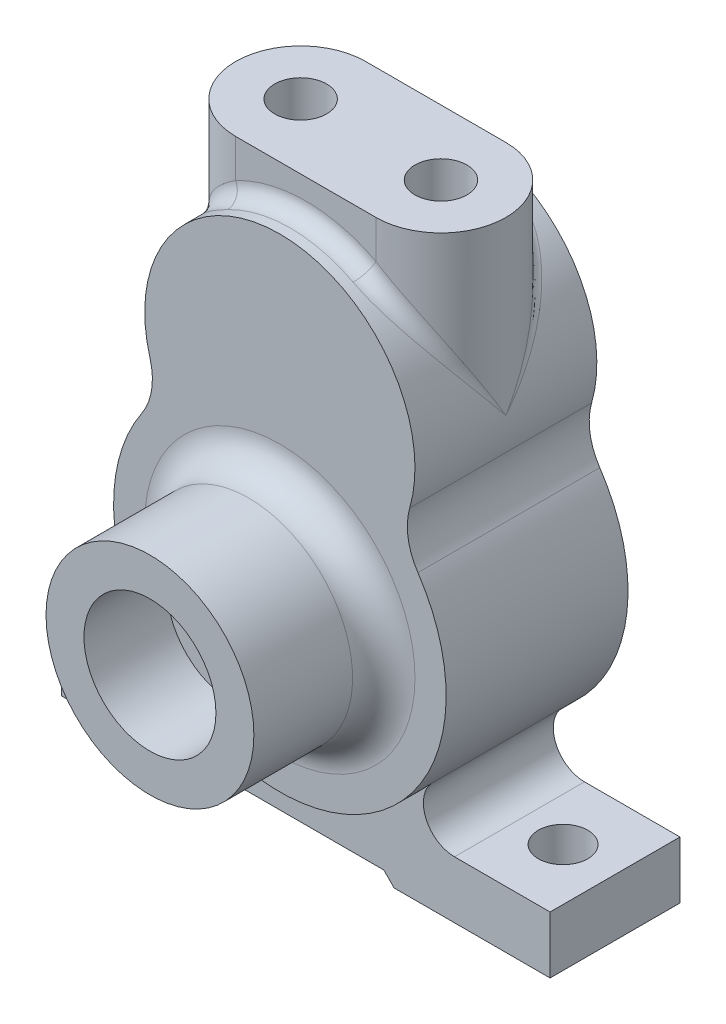
SolidWorks part; units mm, degrees
material "AISI 1020"
ref_plane "Plano frontal" through (0, 0, 0) normal (0, 0, 1) x (1, 0, 0)
ref_plane "Plano superior" through (0, 0, 0) normal (0, 1, 0) x (1, 0, 0)
ref_plane "Plano direito" through (0, 0, 0) normal (1, 0, 0) x (0, 0, -1)
sketch "Esboço1" plane through (0, 0, 0) normal (0, 0, 1) x (1, 0, 0)
  arc A0 (-26.5664, 17.839) -> (26.5664, 17.839) centre (0, 0) ccw
  arc A1 (24.9934, 27.8353) -> (-24.9934, 27.8353) centre (0, 35) ccw
  arc A2 (-24.9934, 27.8353) -> (-26.5664, 17.839) centre (-36.5287, 24.5286) cw
  arc A3 (24.9934, 27.8353) -> (26.5664, 17.839) centre (36.5287, 24.5286) ccw
  dimension "D1" = 64
  dimension "D4" = 52
  dimension "D5" = 12
  dimension "D2" = 0
  dimension "D3" = 35
extrude "Ressalto-extrusão1" add sketch "Esboço1" along normal blind 35
ref_plane "Plano1" through (0, -42, 0) normal (0, 1, 0) x (1, 0, 0)
sketch "Esboço2" plane through (0, -42, 0) normal (0, 1, 0) x (1, 0, 0)
  line L0 (26, 0) -> (-26, 0) construction
  line L1 (-47, -5) -> (47, -5)
  line L2 (-47, -5) -> (-47, -30)
  line L3 (-47, -30) -> (47, -30)
  line L4 (47, -5) -> (47, -30)
  dimension "D1" = 25
  dimension "D2" = 94
  dimension "D3" = 47
  dimension "D4" = 5
extrude "Ressalto-extrusão2" add sketch "Esboço2" along normal blind 11
fillet "Filete1" radius 6 2 edges at (7.9373, -31, 17.5) (-7.9373, -31, 17.5)
ref_plane "Plano2" through (0, 68, 0) normal (0, 1, 0) x (1, 0, 0)
sketch "Esboço3" plane through (0, 68, 0) normal (0, 1, 0) x (1, 0, 0)
  line L0 (-13.5, -17.5) -> (13.5, -17.5) construction
  line L1 (-13.5, -5) -> (13.5, -5)
  line L2 (-13.5, -30) -> (13.5, -30)
  line L3 (26, 0) -> (-26, 0) construction
  arc A0 (-13.5, -5) -> (-13.5, -30) centre (-13.5, -17.5) ccw
  arc A1 (13.5, -30) -> (13.5, -5) centre (13.5, -17.5) ccw
  point P2 (0, -17.5)
  point P7 (-26, -17.5)
  point P8 (26, -17.5)
  dimension "D2" = 52
  dimension "D3" = 12.5
  dimension "D1" = 26
  dimension "D4" = 5
extrude "Ressalto-extrusão3" add sketch "Esboço3" against normal up to surface (10.7795 mm away)
sketch "Esboço4" plane through (0, 68, 0) normal (0, 1, 0) x (1, 0, 0)
  circle A0 centre (-13.5, -17.5) radius 5
  circle A1 centre (13.5, -17.5) radius 5
  dimension "D1" = 10
  dimension "D2" = 10
extrude "Corte-extrusão1" cut sketch "Esboço4" against normal blind 30
sketch "Esboço5" plane through (0, 0, 0) normal (0, 0, -1) x (-1, 0, 0)
  arc A0 (-13.1845, 17.6116) -> (13.1845, 17.6116) centre (0, 0) ccw
  arc A1 (12.3283, 24.8014) -> (-12.3283, 24.8014) centre (0, 35) ccw
  arc A2 (12.3283, 24.8014) -> (13.1845, 17.6116) centre (16.1809, 21.6143) ccw
  arc A3 (-12.3283, 24.8014) -> (-13.1845, 17.6116) centre (-16.1809, 21.6143) cw
  dimension "D1" = 44
  dimension "D2" = 32
  dimension "D3" = 5
extrude "Corte-extrusão2" cut sketch "Esboço5" against normal blind 25
sketch "Esboço6" plane through (0, 0, 35) normal (0, 0, 1) x (1, 0, 0)
  circle A0 centre (0, 0) radius 20
  dimension "D1" = 40
extrude "Ressalto-extrusão4" add sketch "Esboço6" along normal blind 25
sketch "Esboço7" plane through (0, 0, 60) normal (0, 0, 1) x (1, 0, 0)
  circle A0 centre (0, 0) radius 8
  dimension "D1" = 16
extrude "Corte-extrusão3" cut sketch "Esboço7" against normal through all
sketch "Esboço8" plane through (0, 0, 60) normal (0, 0, 1) x (1, 0, 0)
  circle A0 centre (0, 0) radius 12.7
  dimension "D1" = 25.4
extrude "Corte-extrusão4" cut sketch "Esboço8" against normal blind 16
sketch "Esboço9" plane through (0, 0, 30) normal (0, 0, 1) x (1, 0, 0)
  line L0 (-17, -42) -> (-15, -40)
  line L1 (-47, -42) -> (47, -42) construction
  line L2 (-15, -40) -> (15, -40)
  line L3 (15, -40) -> (17, -42)
  line L4 (17, -42) -> (-17, -42)
  dimension "D1" = 2
  dimension "D2" = 17
  dimension "D3" = 34
  dimension "D4" = 45
extrude "Corte-extrusão5" cut sketch "Esboço9" against normal through all
sketch "Esboço10" plane through (0, -42, 0) normal (0, -1, 0) x (1, 0, 0)
  line L0 (-17, 5) -> (-47, 5) construction
  line L1 (47, 5) -> (17, 5) construction
  circle A0 centre (-37, 17.5) radius 4.7625
  circle A1 centre (37, 17.5) radius 4.7625
  dimension "D1" = 37
  dimension "D5" = 9.525
  dimension "D2" = 74
  dimension "D3" = 12.5
  dimension "D4" = 12.5
extrude "Corte-extrusão6" cut sketch "Esboço10" against normal blind 16
sketch "Esboço11" plane through (0, 0, 0) normal (0, 0, -1) x (-1, 0, 0)
  line L0 (0, 0) -> (-39.4712, 0) construction
  line L1 (0, 0) -> (40.0285, 0) construction
  line L2 (0, 0) -> (26.08, -6.9881) construction
  line L3 (0, 0) -> (-26.08, -6.9881) construction
  line L4 (0, 0) -> (0, 35) construction
  line L5 (-11.7949, 35) -> (10.2049, 35) construction
  line L6 (0, 35) -> (14.8492, 49.8492) construction
  line L7 (0, 35) -> (-14.8492, 49.8492) construction
  line L8 (-36.5287, 24.5286) -> (-19.5287, 24.5286) construction
  line L9 (19.5287, 24.5286) -> (36.5287, 24.5286) construction
  circle A0 centre (0, -27) radius 1.5875
  circle A1 centre (-26.08, -6.9881) radius 1.5875
  circle A2 centre (26.08, -6.9881) radius 1.5875
  circle A3 centre (19.5287, 24.5286) radius 1.5875
  circle A4 centre (-19.5287, 24.5286) radius 1.5875
  circle A5 centre (-14.8492, 49.8492) radius 1.5875
  circle A6 centre (14.8492, 49.8492) radius 1.5875
  dimension "D1" = 3.175
  dimension "D2" = 0
  dimension "D3" = 27
  dimension "D4" = 15
  dimension "D5" = 27
  dimension "D6" = 27
  dimension "D7" = 15
  dimension "D8" = 35
  dimension "D9" = 17
  dimension "D10" = 17
  dimension "D13" = 21
  dimension "D14" = 45
  dimension "D15" = 45
  dimension "D16" = 21
extrude "Corte-extrusão7" cut sketch "Esboço11" against normal blind 7
fillet "Filete2" radius 3 6 edges at (22.7562, 47.576, 25.9008) (0, 61, 30) (22.7562, 47.576, 9.0992) (0, 61, 5) (-22.7562, 47.576, 25.9008) (-22.7562, 47.576, 9.0992)
sketch "Esboço12" plane through (0, 0, 25) normal (0, 0, -1) x (-1, 0, 0)
  circle A0 centre (0, 0) radius 18
  dimension "D1" = 36
extrude "Corte-extrusão8" cut sketch "Esboço12" against normal blind 10
sketch3d "3DSketch1"
  point P0 (0, 13, 0)
sketch3d "3DSketch2"
  point P0 (0, 13, 0)
fillet "Filete3" radius 6 1 edges at (20, 0, 35)
sketch "Esboço13" plane through (0, 0, 0) normal (0, 0, -1) x (-1, 0, 0)
  line L1 (-12.8285, 46.3492) -> (-10.8078, 49.8492)
  line L2 (-10.8078, 49.8492) -> (-12.8285, 53.3492)
  line L3 (-12.8285, 53.3492) -> (-16.87, 53.3492)
  line L4 (-16.87, 53.3492) -> (-18.8907, 49.8492)
  line L5 (-18.8907, 49.8492) -> (-16.87, 46.3492)
  line L6 (-16.87, 46.3492) -> (-12.8285, 46.3492)
  line L7 (16.87, 46.3492) -> (18.8907, 49.8492)
  line L8 (18.8907, 49.8492) -> (16.87, 53.3492)
  line L9 (16.87, 53.3492) -> (12.8285, 53.3492)
  line L10 (12.8285, 53.3492) -> (10.8078, 49.8492)
  line L11 (10.8078, 49.8492) -> (12.8285, 46.3492)
  line L12 (12.8285, 46.3492) -> (16.87, 46.3492)
  line L13 (-17.508, 21.0286) -> (-15.4873, 24.5286)
  line L14 (-15.4873, 24.5286) -> (-17.508, 28.0286)
  line L15 (-17.508, 28.0286) -> (-21.5495, 28.0286)
  line L16 (-21.5495, 28.0286) -> (-23.5702, 24.5286)
  line L17 (-23.5702, 24.5286) -> (-21.5495, 21.0286)
  line L18 (-21.5495, 21.0286) -> (-17.508, 21.0286)
  line L19 (-24.0593, -10.4881) -> (-22.0385, -6.9881)
  line L20 (-22.0385, -6.9881) -> (-24.0593, -3.4881)
  line L21 (-24.0593, -3.4881) -> (-28.1007, -3.4881)
  line L22 (-28.1007, -3.4881) -> (-30.1214, -6.9881)
  line L23 (-30.1214, -6.9881) -> (-28.1007, -10.4881)
  line L24 (-28.1007, -10.4881) -> (-24.0593, -10.4881)
  line L25 (2.0207, -30.5) -> (4.0415, -27)
  line L26 (4.0415, -27) -> (2.0207, -23.5)
  line L27 (2.0207, -23.5) -> (-2.0207, -23.5)
  line L28 (-2.0207, -23.5) -> (-4.0415, -27)
  line L29 (-4.0415, -27) -> (-2.0207, -30.5)
  line L30 (-2.0207, -30.5) -> (2.0207, -30.5)
  line L31 (28.1007, -10.4881) -> (30.1214, -6.9881)
  line L32 (30.1214, -6.9881) -> (28.1007, -3.4881)
  line L33 (28.1007, -3.4881) -> (24.0593, -3.4881)
  line L34 (24.0593, -3.4881) -> (22.0385, -6.9881)
  line L35 (22.0385, -6.9881) -> (24.0593, -10.4881)
  line L36 (24.0593, -10.4881) -> (28.1007, -10.4881)
  line L37 (21.5495, 21.0286) -> (23.5702, 24.5286)
  line L38 (23.5702, 24.5286) -> (21.5495, 28.0286)
  line L39 (21.5495, 28.0286) -> (17.508, 28.0286)
  line L40 (17.508, 28.0286) -> (15.4873, 24.5286)
  line L41 (15.4873, 24.5286) -> (17.508, 21.0286)
  line L42 (17.508, 21.0286) -> (21.5495, 21.0286)
  circle A0 centre (-14.8492, 49.8492) radius 3.5 construction
  circle A1 centre (14.8492, 49.8492) radius 3.5 construction
  circle A2 centre (-19.5287, 24.5286) radius 3.5 construction
  circle A3 centre (-26.08, -6.9881) radius 3.5 construction
  circle A4 centre (0, -27) radius 3.5 construction
  circle A5 centre (26.08, -6.9881) radius 3.5 construction
  circle A6 centre (19.5287, 24.5286) radius 3.5 construction
  dimension "D1" = 7
extrude "Corte-extrusão9" cut sketch "Esboço13" against normal blind 3
